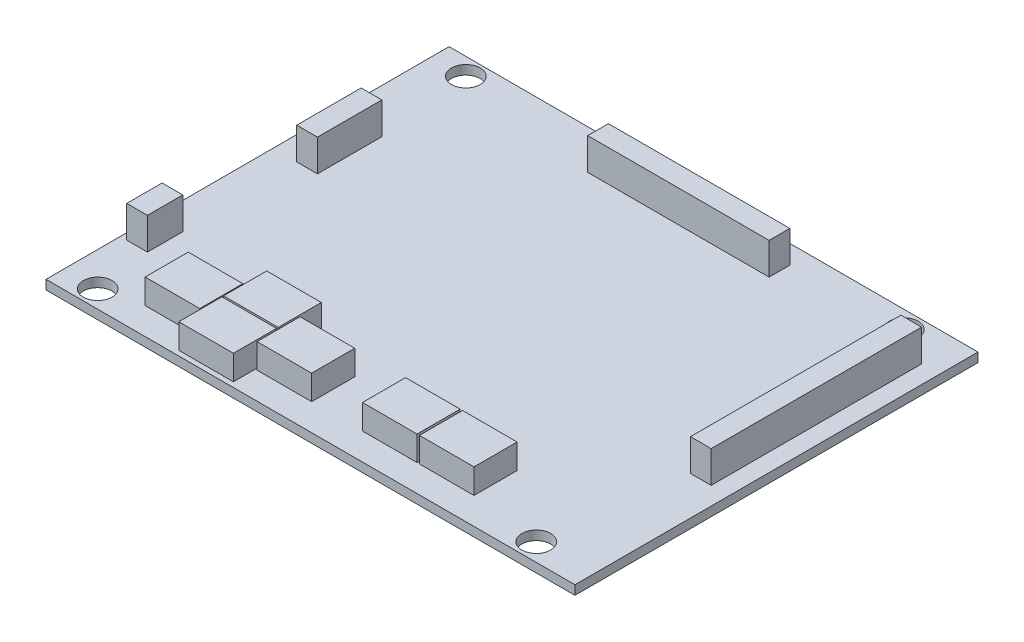
SolidWorks part; units mm, degrees
ref_plane "Front Plane" through (0, 0, 0) normal (0, 0, 1) x (1, 0, 0)
ref_plane "Top Plane" through (0, 0, 0) normal (0, 1, 0) x (1, 0, 0)
ref_plane "Right Plane" through (0, 0, 0) normal (1, 0, 0) x (0, 0, -1)
sketch "Sketch1" plane through (0, 0, 0) normal (0, 1, 0) x (1, 0, 0)
  line L1 (0, 0) -> (92, 0)
  line L2 (0, 0) -> (0, 70.1)
  line L3 (0, 70.1) -> (92, 70.1)
  line L4 (92, 0) -> (92, 70.1)
  circle A0 centre (5.92, 3.07) radius 2.5
  circle A1 centre (82.16, 3.11) radius 2.5
  circle A2 centre (82.16, 67.05) radius 2.5
  circle A3 centre (5.92, 67.1) radius 2.5
  dimension "D3" = 5.92
  dimension "D1" = 92
  dimension "D2" = 70.1
  dimension "D4" = 3.07
  dimension "D5" = 9.84
  dimension "D6" = 3.11
  dimension "D7" = 9.84
  dimension "D8" = 3.05
  dimension "D9" = 3
  dimension "D10" = 5.92
extrude "Y+ PCB extr" add sketch "Sketch1" along normal blind 1.6
sketch "Sketch2" plane through (0, 1.6, 0) normal (0, 1, 0) x (1, 0, 0)
  line L0 (0, 70.1) -> (0, 0) construction
  line L1 (31, 66.82) -> (62.55, 66.82)
  line L2 (31, 66.82) -> (31, 63.22)
  line L3 (31, 63.22) -> (62.55, 63.22)
  line L4 (62.55, 66.82) -> (62.55, 63.22)
  line L5 (4.12, 50.69) -> (7.72, 50.69)
  line L6 (4.12, 50.69) -> (4.12, 39.49)
  line L7 (4.12, 39.49) -> (7.72, 39.49)
  line L8 (7.72, 50.69) -> (7.72, 39.49)
  line L9 (1.12, 19.07) -> (4.72, 19.07)
  line L10 (1.12, 19.07) -> (1.12, 12.92)
  line L11 (1.12, 12.92) -> (4.72, 12.92)
  line L12 (4.72, 19.07) -> (4.72, 12.92)
  line L13 (85.28, 63.41) -> (88.88, 63.41)
  line L14 (85.28, 63.41) -> (85.28, 26.81)
  line L15 (85.28, 26.81) -> (88.88, 26.81)
  line L16 (88.88, 63.41) -> (88.88, 26.81)
  line L17 (92, 70.1) -> (0, 70.1) construction
  line L18 (92, 0) -> (92, 70.1) construction
  line L19 (0, 0) -> (92, 0) construction
  dimension "D1" = 31
  dimension "D2" = 3.28
  dimension "D3" = 3.6
  dimension "D4" = 31.55
  dimension "D5" = 6.69
  dimension "D6" = 3.12
  dimension "D7" = 3.6
  dimension "D8" = 36.6
  dimension "D9" = 19.41
  dimension "D10" = 4.12
  dimension "D11" = 11.2
  dimension "D12" = 3.6
  dimension "D13" = 3.6
  dimension "D14" = 6.15
  dimension "D15" = 1.12
  dimension "D16" = 12.92
extrude "Y+ headers extr" add sketch "Sketch2" along normal blind 5.54
sketch "Sketch3" plane through (0, 1.6, 0) normal (0, 1, 0) x (1, 0, 0)
  line L1 (12.57, 12.17) -> (22.07, 12.17)
  line L2 (12.57, 12.17) -> (12.57, 4.67)
  line L3 (12.57, 4.67) -> (22.07, 4.67)
  line L4 (22.07, 12.17) -> (22.07, 4.67)
  line L24 (0, 70.1) -> (0, 0) construction
  line L25 (0, 0) -> (92, 0) construction
  line L26 (22.23, 8.36) -> (31.73, 8.36)
  line L27 (22.23, 8.36) -> (22.23, 0.86)
  line L28 (22.23, 0.86) -> (31.73, 0.86)
  line L29 (31.73, 8.36) -> (31.73, 0.86)
  line L30 (22.23, 16.16) -> (31.73, 16.16)
  line L31 (22.23, 16.16) -> (22.23, 8.66)
  line L32 (22.23, 8.66) -> (31.73, 8.66)
  line L33 (31.73, 16.16) -> (31.73, 8.66)
  line L34 (32.03, 12.17) -> (41.53, 12.17)
  line L35 (32.03, 12.17) -> (32.03, 4.67)
  line L36 (32.03, 4.67) -> (41.53, 4.67)
  line L37 (41.53, 12.17) -> (41.53, 4.67)
  line L38 (50.37, 12.17) -> (59.87, 12.17)
  line L39 (50.37, 12.17) -> (50.37, 4.67)
  line L40 (50.37, 4.67) -> (59.87, 4.67)
  line L41 (59.87, 12.17) -> (59.87, 4.67)
  line L42 (92, 0) -> (92, 70.1) construction
  line L43 (60.27, 12.17) -> (69.77, 12.17)
  line L44 (60.27, 12.17) -> (60.27, 4.67)
  line L45 (60.27, 4.67) -> (69.77, 4.67)
  line L46 (69.77, 12.17) -> (69.77, 4.67)
  dimension "D1" = 9.5
  dimension "D2" = 7.5
  dimension "D3" = 12.57
  dimension "D4" = 4.67
  dimension "D5" = 9.5
  dimension "D6" = 7.5
  dimension "D7" = 22.23
  dimension "D8" = 0.86
  dimension "D9" = 9.5
  dimension "D10" = 7.5
  dimension "D11" = 22.23
  dimension "D12" = 8.66
  dimension "D13" = 9.5
  dimension "D14" = 7.5
  dimension "D15" = 4.67
  dimension "D16" = 32.03
  dimension "D17" = 9.5
  dimension "D18" = 7.5
  dimension "D19" = 32.13
  dimension "D20" = 4.67
  dimension "D21" = 9.5
  dimension "D22" = 7.5
  dimension "D23" = 4.67
  dimension "D24" = 22.23
extrude "Y+ switches extr" add sketch "Sketch3" along normal blind 4.3
sketch "Sketch4" plane through (0, 0, 0) normal (0, -1, 0) x (1, 0, 0)
  line L1 (74.14, -19.8) -> (81.54, -19.8)
  line L2 (74.14, -19.8) -> (74.14, -9.4)
  line L3 (74.14, -9.4) -> (81.54, -9.4)
  line L4 (81.54, -19.8) -> (81.54, -9.4)
  line L6 (0, 0) -> (92, 0) construction
  line L7 (92, 0) -> (92, -70.1) construction
  dimension "D1" = 9.4
  dimension "D2" = 10.46
  dimension "D3" = 7.4
  dimension "D4" = 10.4
extrude "Y- U4 extr" add sketch "Sketch4" along normal blind 2.6
